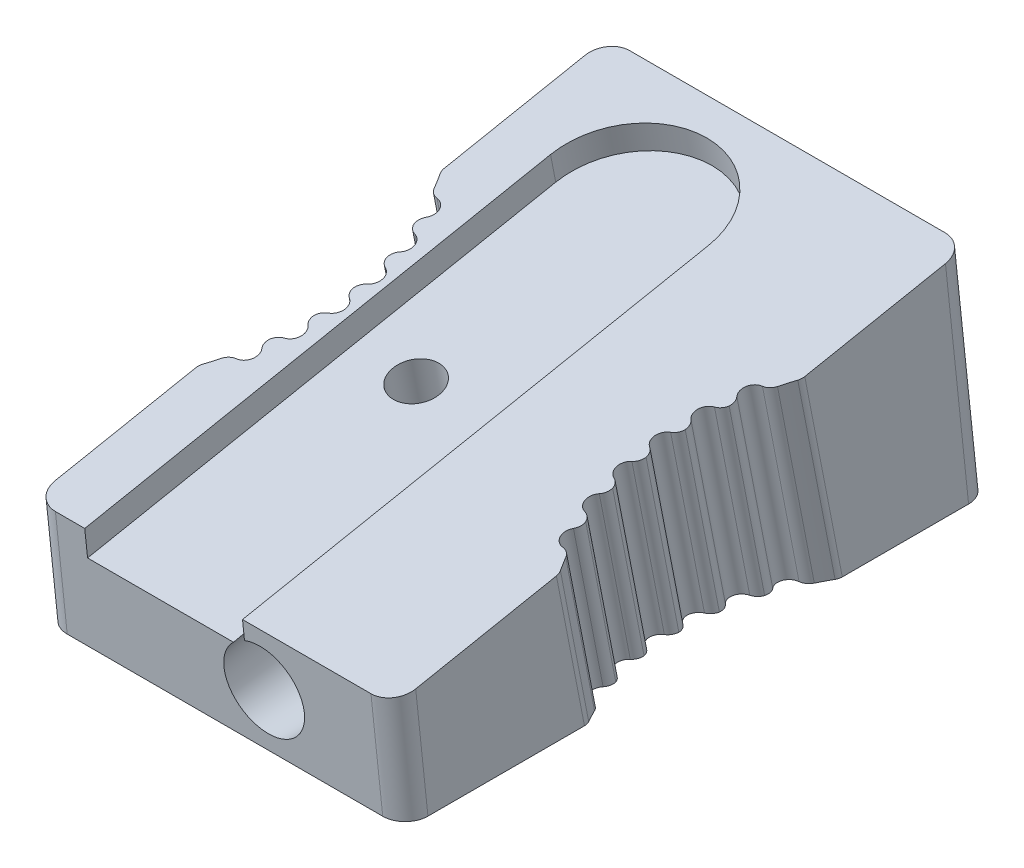
SolidWorks part; units mm, degrees
ref_plane "Front Plane" through (0, 0, 0) normal (0, 0, 1) x (1, 0, 0)
ref_plane "Top Plane" through (0, 0, 0) normal (0, 1, 0) x (1, 0, 0)
ref_plane "Right Plane" through (0, 0, 0) normal (1, 0, 0) x (0, 0, -1)
sketch "Sketch1" plane through (0, 0, 0) normal (1, 0, 0) x (0, 0, -1)
  line L0 (0, 0) -> (-26, 0)
  line L1 (-26, 0) -> (-26.5226, 4.9726)
  line L2 (-26.5226, 4.9726) -> (-1.0453, 9.9452)
  line L3 (-1.0453, 9.9452) -> (0, 0)
  dimension "D1" = 26
  dimension "D2" = 84
  dimension "D3" = 10
  dimension "D4" = 5
extrude "Boss-Extrude1" add sketch "Sketch1" along normal blind 16
sketch "Sketch2" plane through (0, 9.7768, 1.9082) normal (0, 0.9815, 0.1916) x (1, 0, 0)
  line L0 (8, 0.8792) -> (8, -25.0789) construction
  line L1 (16, 0.8792) -> (0, 0.8792) construction
  line L2 (16, -25.0789) -> (0, -25.0789) construction
  line L3 (0, 0.8792) -> (0, -25.0789) construction
  line L7 (0, -6.6208) -> (0, -17.5789)
  line L9 (16, -6.6208) -> (16, -17.5789)
  arc A0 (0, -6.6208) -> (0, -17.5789) centre (-9.2567, -12.0998) cw
  arc A1 (16, -6.6208) -> (16, -17.5789) centre (25.2567, -12.0998) ccw
  dimension "D3" = 13
  dimension "D1" = 7.5
  dimension "D2" = 7.5
extrude "Cut-Extrude1" cut sketch "Sketch2" against normal up to surface (8.669 mm away) up to face at (8, 0, 13)
ref_plane "Plane1" through (10, 0, 0) normal (1, 0, 0) x (0, 0, -1)
sketch "Sketch3" plane through (10, 0, 0) normal (1, 0, 0) x (0, 0, -1)
  line L0 (-26.2613, 2.4863) -> (-0.5226, 4.9726)
  line L1 (-26.5226, 4.9726) -> (-26, 0) construction
  line L2 (0, 0) -> (-1.0453, 9.9452) construction
  line L3 (-27.2567, 2.3902) -> (0.4728, 5.0688)
  line L4 (0.4728, 5.0688) -> (0.0546, 9.0469)
  line L5 (0.0546, 9.0469) -> (-27.4344, 4.0808)
  line L6 (-27.4344, 4.0808) -> (-27.2567, 2.3902)
  line L7 (-27.2567, 2.3902) -> (-27.4344, 4.0808)
  line L8 (0.9945, 0.1045) -> (-0.0508, 10.0497)
  line L9 (0.9945, 0.1045) -> (-0.0508, 10.0497)
  line L10 (0.4728, 5.0688) -> (0.0546, 9.0469)
  line L11 (-27.5172, 4.8681) -> (-26.9945, -0.1045)
  line L12 (-27.5172, 4.8681) -> (-26.9945, -0.1045)
  point P12 (-0.9321, 8.8686)
  point P15 (-26.4476, 4.2591)
  point P16 (0, 0)
  dimension "D3" = 4
  dimension "D4" = 1.7
  dimension "D1" = 1
  dimension "D2" = 1
revolve "Cut-Revolve2" cut sketch "Sketch3" angle 360 about L3 region at (10, 5.4037, 11.6842)
sketch "Sketch4" plane through (0, 9.7768, 1.9082) normal (0, 0.9815, 0.1916) x (1, 0, 0)
  line L0 (2.3, -25.0789) -> (2.3, -4.0208)
  line L1 (16, -25.0789) -> (0, -25.0789) construction
  line L2 (9.3, -4.0208) -> (9.3, -25.0789)
  line L3 (9.3, -25.0789) -> (2.3, -25.0789)
  line L4 (0, -17.5789) -> (0, -25.0789) construction
  line L7 (16, 0.8792) -> (0, 0.8792) construction
  arc A0 (2.3, -4.0208) -> (9.3, -4.0208) centre (5.8, -4.0208) cw
  point P10 (5.8, -0.5208)
  dimension "D2" = 1.4
  dimension "D1" = 2.3
  dimension "D3" = 7
extrude "Cut-Extrude4" cut sketch "Sketch4" against normal blind 1.2
sketch "Sketch6" plane through (0, -4.8042, 24.6144) normal (0, 0.1916, -0.9815) x (-1, 0, 0)
  line L1 (-2.3, 9.9613) -> (-9.3, 9.9613)
  line L2 (-2.3, 9.9613) -> (-2.3, 8.7613)
  line L3 (-2.3, 8.7613) -> (-9.3, 8.7613)
  line L4 (-9.3, 9.9613) -> (-9.3, 8.7613)
extrude "Cut-Extrude5" cut sketch "Sketch6" against normal blind 1.2
hole_wizard "M2.5x0.45 Tapped Hole2" positions "3DSketch2" profile "Sketch10" tap size "M2.5x0.45" standard "ANSI Metric"
sketch3d "3DSketch2"
  line L0 (8.775, 3.7745, 26.3967) -> (2.3, 3.7745, 26.3967) construction
  line L1 (2.3, 7.8288, 5.6247) -> (2.3, 3.7745, 26.3967) construction
  point P0 (5.1, 6.0733, 14.619)
  dimension "D1" = 12
  dimension "D2" = 2.8
sketch "Sketch10" plane through (5.1, 6.0733, 14.619) normal (1, 0, 0) x (0, -0.1916, 0.9815)
  line L0 (0, 0) -> (0, 4.6159)
  line L1 (0, 4.6159) -> (1.025, 4)
  line L2 (1.025, 4) -> (1.025, 0)
  line L5 (1.025, 0) -> (0, 0)
  line L10 (0, 4.6159) -> (-1.025, 4) construction
  line L11 (0, -6.35) -> (0, 107.95) construction
  dimension "Tap Drill Dia." = 2.05
  dimension "Tap Drill Depth" = 4
  dimension "Drill Angle" = 118
cosmetic thread "Hole Thread2" parameters "D1"=4, "D2"=2.5
sketch "Sketch11" plane through (0, 9.7768, 1.9082) normal (0, 0.9815, 0.1916) x (1, 0, 0)
  line L0 (8, 0.8792) -> (8, -31.8218) construction
  line L1 (16, 0.8792) -> (0, 0.8792) construction
  circle A0 centre (0.7291, -8.101) radius 0.5
  arc A1 (0, -17.5789) -> (0, -6.6208) centre (-9.2567, -12.0998) ccw construction
  circle A2 centre (1.2232, -9.6753) radius 0.5
  circle A3 centre (1.4707, -11.3066) radius 0.5
  circle A4 centre (1.4658, -12.9566) radius 0.5
  circle A5 centre (1.2086, -14.5864) radius 0.5
  circle A6 centre (0.7052, -16.1577) radius 0.5
  circle A7 centre (15.2948, -16.1577) radius 0.5
  circle A8 centre (14.7914, -14.5864) radius 0.5
  circle A9 centre (14.5342, -12.9566) radius 0.5
  circle A10 centre (14.5293, -11.3066) radius 0.5
  circle A11 centre (14.7768, -9.6753) radius 0.5
  circle A12 centre (15.2709, -8.101) radius 0.5
  dimension "D1" = 1
  dimension "D7" = 1.65
  dimension "D2" = 1.65
  dimension "D3" = 1.65
  dimension "D4" = 1.65
  dimension "D5" = 1.65
  dimension "D6" = 1.65
extrude "Cut-Extrude6" cut sketch "Sketch11" against normal through all
fillet "Fillet1" radius 1 4 edges at (0, 4.9726, 0.5226) (16, 4.9726, 0.5226) (16, 2.4863, 26.2613) (0, 2.4863, 26.2613)
fillet "Fillet3" radius 0.5 28 edges at (0, 4.2542, 7.5761) (0.5325, 4.1565, 8.5967) (0.9041, 4.0676, 9.5249) (1.0992, 4.0081, 10.1466) (1.3245, 3.9148, 11.1208) (1.4223, 3.8531, 11.7649) (1.496, 3.7576, 12.7621) (1.4144, 3.5998, 14.4104) (1.3129, 3.5381, 15.054) (1.0818, 3.445, 16.0268) (0.883, 3.3855, 16.6473) (0.5059, 3.2969, 17.5733) (0, 3.2047, 18.5361) (16, 3.2047, 18.5361) (15.4941, 3.2969, 17.5733) (15.117, 3.3855, 16.6473) (14.9182, 3.445, 16.0268) (14.6871, 3.5381, 15.054) (14.5856, 3.5998, 14.4104) (14.5059, 3.6952, 13.4137) (14.504, 3.7576, 12.7621) (14.5777, 3.8531, 11.7649) (14.6755, 3.9148, 11.1208) (14.9008, 4.0081, 10.1466) (15.0959, 4.0676, 9.5249) (15.4675, 4.1565, 8.5967) (16, 4.2542, 7.5761) (1.4941, 3.6952, 13.4137)
